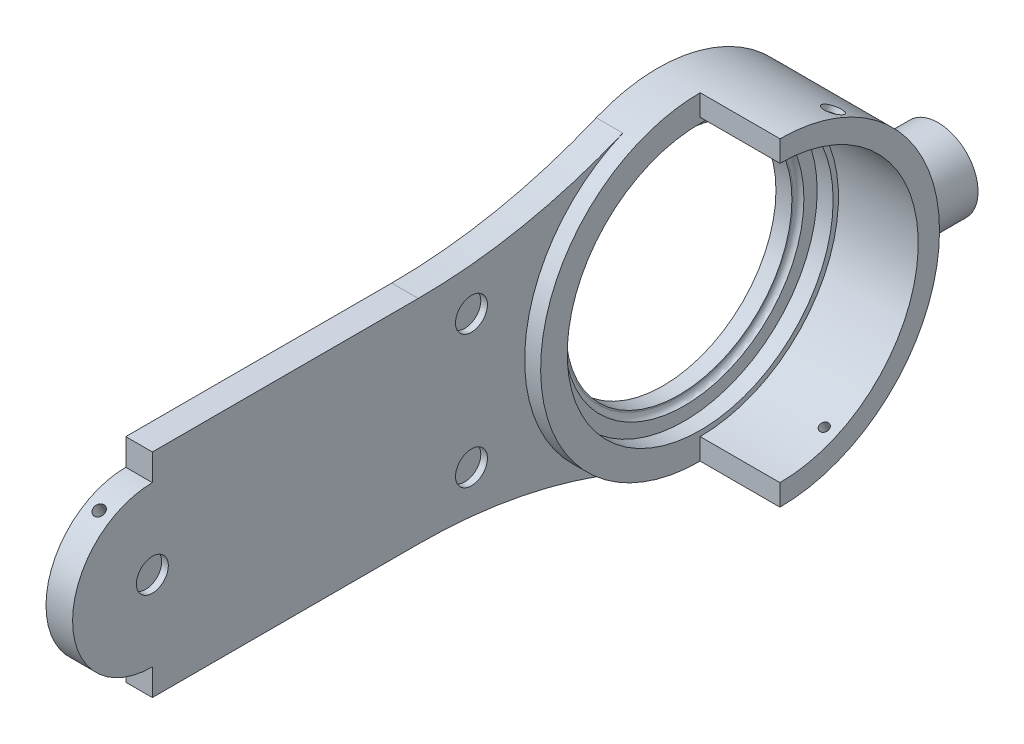
SolidWorks part; units mm, degrees
ref_plane "Front Plane" through (0, 0, 0) normal (0, 0, 1) x (1, 0, 0)
ref_plane "Top Plane" through (0, 0, 0) normal (0, 1, 0) x (1, 0, 0)
ref_plane "Right Plane" through (0, 0, 0) normal (1, 0, 0) x (0, 0, -1)
sketch "Sketch1" plane through (0, 0, 0) normal (1, 0, 0) x (0, 0, -1)
  line L0 (0, 0) -> (-200, 0) construction
  line L1 (-200, 40) -> (-200, -40) construction
  line L2 (-100, 40) -> (-100, -40) construction
  line L3 (-100, 40) -> (-200, 40)
  line L4 (-100, -40) -> (-200, -40)
  circle A0 centre (0, 0) radius 60
  circle A1 centre (0, 0) radius 45
  circle A2 centre (-200, 0) radius 40
  arc A3 (-100, 40) -> (-23.0769, 55.3846) centre (-100, 240) ccw
  arc A4 (-100, -40) -> (-23.0769, -55.3846) centre (-100, -240) cw
  circle A5 centre (-100, 0) radius 40 construction
  dimension "D1" = 120
  dimension "D2" = 90
  dimension "D4" = 80
  dimension "D3" = 200
extrude "Boss-Extrude3" add sketch "Sketch1" along normal blind 10 contours A0 A1 | A2 A0 | A2 region at (0, 0, 109.7273) region at (0, 0, 200) region at (0, 48.511, -32.3407)
sketch "Sketch4" plane through (10, 0, 0) normal (1, 0, 0) x (0, 0, -1)
  circle A0 centre (0, 0) radius 60
  circle A1 centre (0, 0) radius 50
  arc A2 (-23.0769, -55.3846) -> (-23.0769, 55.3846) centre (0, 0) ccw construction
  dimension "D1" = 100
extrude "Boss-Extrude4" add sketch "Sketch4" along normal blind 6
sketch "Sketch5" plane through (0, 0, 0) normal (-1, 0, 0) x (0, 0, 1)
  circle A0 centre (0, 0) radius 45 construction
  circle A1 centre (0, 0) radius 45
  circle A2 centre (0, 0) radius 42.5
  dimension "D1" = 85
extrude "Boss-Extrude5" add sketch "Sketch5" against normal offset from surface (8 mm away) 2 up to face at (10, 0, -45)
fillet "Fillet1" radius 2 1 edges at (8, 0, -45)
sketch "Sketch6" plane through (0, 0, 0) normal (-1, 0, 0) x (0, 0, 1)
  circle A0 centre (0, 0) radius 42.5 construction
  circle A1 centre (0, 0) radius 42.5
  circle A2 centre (0, 0) radius 52.5
  dimension "D1" = 105
extrude "Cut-Extrude2" cut sketch "Sketch6" against normal blind 2
sketch "Sketch7" plane through (16, 0, 0) normal (1, 0, 0) x (0, 0, -1)
  line L0 (0, 60) -> (0, 50)
  line L1 (0, -50) -> (0, -60)
  circle A0 centre (0, 0) radius 60 construction
  circle A1 centre (0, 0) radius 50 construction
  circle A2 centre (0, 0) radius 50 construction
  arc A3 (0, -60) -> (0, 60) centre (0, 0) ccw
  arc A4 (0, -50) -> (0, 50) centre (0, 0) ccw
  arc A5 (0, -52) -> (0, 52) centre (0, 0) ccw
  circle M1 centre (0, 0) radius 60
  dimension "D1" = 2
extrude "Boss-Extrude6" add sketch "Sketch7" along normal blind 30 contours A5 L1 L0 M1 region at (16, 41.4777, -41.4777)
ref_plane "Plane2" through (0, 0, -60) normal (0, 0, -1) x (-1, 0, 0)
sketch "Sketch8" plane through (0, 0, -60) normal (0, 0, -1) x (-1, 0, 0)
  line L0 (-5, 0) -> (-46, 0) construction
  line L1 (-5, 0) -> (0, 0) construction
  line L3 (-46, 60) -> (-46, -60) construction
  circle A0 centre (-25.5, 0) radius 20.5
  dimension "D1" = 5
extrude "Boss-Extrude7" add sketch "Sketch8" against normal up to surface up to face at (5, 0, 11.5385)
sketch "Sketch9" plane through (0, 0, -60) normal (0, 0, -1) x (-1, 0, 0)
  circle A0 centre (-25.5, 0) radius 15
  dimension "D1" = 30
extrude "Boss-Extrude8" add sketch "Sketch9" along normal blind 20 contours A0
sketch "Sketch12" plane through (10, 0, 0) normal (1, 0, 0) x (0, 0, -1)
  line L0 (-200, 30) -> (-200, 40)
  line L2 (-200, -40) -> (-200, -30)
  arc A0 (-200, 40) -> (-200, -40) centre (-200, 0) ccw
  arc A1 (-200, 30) -> (-200, -30) centre (-200, 0) ccw
  dimension "D1" = 30
extrude "Cut-Extrude3" cut sketch "Sketch12" against normal through all
hole_wizard "CBORE for M3 Hexagon head bolts-Full thread-grades AB2" positions "3DSketch4" profile "Sketch14" counterbore size "M3" standard "GB" end condition up to next
sketch3d "3DSketch4"
  point P0 (41, 54.5436, -25)
  point P2 (41, -54.5436, -25)
  dimension "D1" = 5
  dimension "D2" = 5
  dimension "D3" = 25
  dimension "D4" = 25
sketch "Sketch14" plane through (41, 54.5436, -25) normal (1, 0, 0) x (0, 0.4167, 0.9091)
  line L0 (0, 0) -> (0, 8)
  line L1 (0, 8) -> (1.7, 8)
  line L3 (1.7, 8) -> (1.7, 2)
  line L4 (1.7, 2) -> (3.5, 2)
  line L5 (3.5, 2) -> (3.5, 0)
  line L7 (3.5, 0) -> (0, 0)
  line L11 (0, -6.35) -> (0, 107.95) construction
  dimension "Thru Hole Dia." = 3.4
  dimension "Thru Hole Depth" = 8
  dimension "C'Bore Dia." = 7
  dimension "C'Bore Depth" = 2
sketch3d "3DSketch6"
  circle A0 centre (5, -32.909, 219) radius 1.7 construction
  circle A1 centre (5, 32.909, 219) radius 1.7 construction
  circle A2 centre (5, -32.909, 219) radius 1.7
  circle A3 centre (5, 32.909, 219) radius 1.7
  point P0 (5.23, -14.1961, 226.4286)
  point P3 (5, -34.3812, 219.85)
  point P6 (5, 34.3812, 219.85)
  point P8 (5, -34.3812, 219.85)
  point P10 (5, 34.3812, 219.85)
ref_plane "Plane3" through (0, 119.5115, 69) normal (0, 0.866, 0.5) x (1, 0, 0)
ref_plane "Plane4" through (0, -119.5115, 69) normal (0, -0.866, 0.5) x (-1, 0, 0)
sketch "Sketch17" plane through (0, -119.5115, 69) normal (0, -0.866, 0.5) x (-1, 0, 0)
  circle A0 centre (-5, -173.2051) radius 2.05
  dimension "D1" = 4.1
extrude "Cut-Extrude4" cut sketch "Sketch17" against normal blind 15
sketch "Sketch18" plane through (0, 119.5115, 69) normal (0, 0.866, 0.5) x (1, 0, 0)
  circle A0 centre (5, -173.2051) radius 2.05
  dimension "D1" = 4.1
extrude "Cut-Extrude5" cut sketch "Sketch18" against normal blind 15
sketch "Sketch19" plane through (10, 0, 0) normal (1, 0, 0) x (0, 0, -1)
  circle A0 centre (-200, 0) radius 6
  point P0 (-200, 0)
  dimension "D1" = 12
extrude "Cut-Extrude6" cut sketch "Sketch19" against normal blind 2.5
sketch "Sketch20" plane through (10, 0, 0) normal (1, 0, 0) x (0, 0, -1)
  line L0 (-69.9723, 0) -> (-95.1108, 0) construction
  circle A0 centre (-80, -25) radius 6
  circle A1 centre (-80, 25) radius 6
  arc A2 (-23.0769, 55.3846) -> (-23.0769, -55.3846) centre (0, 0) ccw construction
  dimension "D1" = 50
  dimension "D3" = 80
  dimension "D2" = 25
extrude "Cut-Extrude7" cut sketch "Sketch20" against normal blind 2.5
